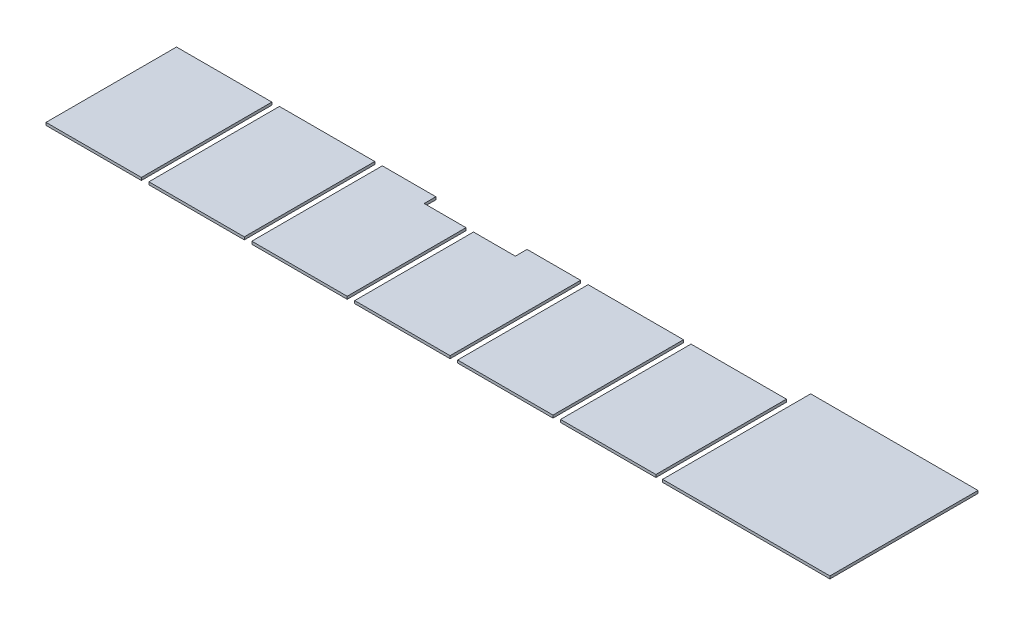
SolidWorks part; units mm, degrees
ref_plane "Front Plane" through (0, 0, 0) normal (0, 0, 1) x (1, 0, 0)
ref_plane "Top Plane" through (0, 0, 0) normal (0, 1, 0) x (1, 0, 0)
ref_plane "Right Plane" through (0, 0, 0) normal (1, 0, 0) x (0, 0, -1)
sketch "Sketch2" plane through (0, 0, 0) normal (0, 1, 0) x (1, 0, 0)
  line L4 (3073.4, 2044.7) -> (1625.6, 2044.7)
  line L5 (1625.6, 2044.7) -> (1625.6, 63.5)
  line L6 (1625.6, 63.5) -> (3073.4, 63.5)
  line L7 (3073.4, 63.5) -> (3073.4, 2044.7)
  line L8 (3073.4, 2044.7) -> (1625.6, 2044.7)
  line L9 (1625.6, 2044.7) -> (1625.6, 63.5)
  line L10 (1625.6, 63.5) -> (3073.4, 63.5)
  line L11 (3073.4, 63.5) -> (3073.4, 2044.7)
  line L12 (1511.3, 2044.7) -> (63.5, 2044.7)
  line L13 (63.5, 2044.7) -> (63.5, 63.5)
  line L14 (63.5, 63.5) -> (1511.3, 63.5)
  line L15 (1511.3, 63.5) -> (1511.3, 2044.7)
  line L16 (1511.3, 2044.7) -> (63.5, 2044.7)
  line L17 (63.5, 2044.7) -> (63.5, 63.5)
  line L18 (63.5, 63.5) -> (1511.3, 63.5)
  line L19 (1511.3, 63.5) -> (1511.3, 2044.7)
  line L20 (9321.8, 2044.7) -> (7874, 2044.7)
  line L21 (7874, 2044.7) -> (7874, 63.5)
  line L22 (7874, 63.5) -> (9321.8, 63.5)
  line L23 (9321.8, 63.5) -> (9321.8, 2044.7)
  line L24 (9321.8, 2044.7) -> (7874, 2044.7)
  line L25 (7874, 2044.7) -> (7874, 63.5)
  line L26 (7874, 63.5) -> (9321.8, 63.5)
  line L27 (9321.8, 63.5) -> (9321.8, 2044.7)
  line L28 (7759.7, 63.5) -> (7759.7, 2044.7)
  line L29 (6311.9, 63.5) -> (7759.7, 63.5)
  line L30 (6311.9, 2044.7) -> (6311.9, 63.5)
  line L31 (7759.7, 2044.7) -> (6311.9, 2044.7)
  line L32 (7759.7, 63.5) -> (7759.7, 2044.7)
  line L33 (6311.9, 63.5) -> (7759.7, 63.5)
  line L34 (6311.9, 2044.7) -> (6311.9, 63.5)
  line L35 (7759.7, 2044.7) -> (6311.9, 2044.7)
  line L36 (11976.1, 2298.7) -> (9436.1, 2298.7)
  line L37 (11976.1, 50.8) -> (11976.1, 2298.7)
  line L38 (6197.6, 2044.7) -> (5384.8, 2044.7)
  line L39 (6197.6, 63.5) -> (6197.6, 2044.7)
  line L40 (4749.8, 63.5) -> (6197.6, 63.5)
  line L41 (4749.8, 1866.9) -> (4749.8, 63.5)
  line L42 (5384.8, 1866.9) -> (4749.8, 1866.9)
  line L43 (5384.8, 2044.7) -> (5384.8, 1866.9)
  line L44 (6197.6, 2044.7) -> (5384.8, 2044.7)
  line L45 (6197.6, 63.5) -> (6197.6, 2044.7)
  line L46 (4749.8, 63.5) -> (6197.6, 63.5)
  line L47 (4749.8, 1866.9) -> (4749.8, 63.5)
  line L48 (5384.8, 1866.9) -> (4749.8, 1866.9)
  line L49 (5384.8, 2044.7) -> (5384.8, 1866.9)
  line L50 (3187.7, 2044.7) -> (3187.7, 63.5)
  line L51 (4000.5, 2044.7) -> (3187.7, 2044.7)
  line L52 (4000.5, 1866.9) -> (4000.5, 2044.7)
  line L53 (4635.5, 1866.9) -> (4000.5, 1866.9)
  line L54 (4635.5, 63.5) -> (4635.5, 1866.9)
  line L55 (3187.7, 63.5) -> (4635.5, 63.5)
  line L56 (3187.7, 2044.7) -> (3187.7, 63.5)
  line L57 (4000.5, 2044.7) -> (3187.7, 2044.7)
  line L58 (4000.5, 1866.9) -> (4000.5, 2044.7)
  line L59 (4635.5, 1866.9) -> (4000.5, 1866.9)
  line L60 (4635.5, 63.5) -> (4635.5, 1866.9)
  line L61 (3187.7, 63.5) -> (4635.5, 63.5)
  line L62 (9436.1, 50.8) -> (11976.1, 50.8)
  line L63 (9436.1, 2298.7) -> (9436.1, 50.8)
  line L64 (11976.1, 2298.7) -> (9436.1, 2298.7)
  line L65 (11976.1, 50.8) -> (11976.1, 2298.7)
  line L66 (9436.1, 50.8) -> (11976.1, 50.8)
  line L67 (9436.1, 2298.7) -> (9436.1, 50.8)
  dimension "D1" = 0
  dimension "D2" = 0
  dimension "D3" = 0
  dimension "D4" = 0
  dimension "D5" = 0
  dimension "D6" = 0
  dimension "D7" = 0
extrude "Boss-Extrude1" add sketch "Sketch2" along normal up to surface (40.64 mm away) contours L18 L19 L16 L17 | L10 L11 L8 L9 | L56 L61 L60 L59 L58 L57 | L44 L49 L48 L47 L46 L45 | L32 L35 L34 L33 | L26 L27 L24 L25 | L64 L67 L66 L65 region at (2349.5, 0, -1054.1) region at (787.4, 0, -1054.1) region at (8597.9, 0, -1054.1) region at (7035.8, 0, -1054.1) region at (10706.1, 0, -1174.75) region at (5490.3518, 0, -1017.1537) region at (3894.9482, 0, -1017.1537)
